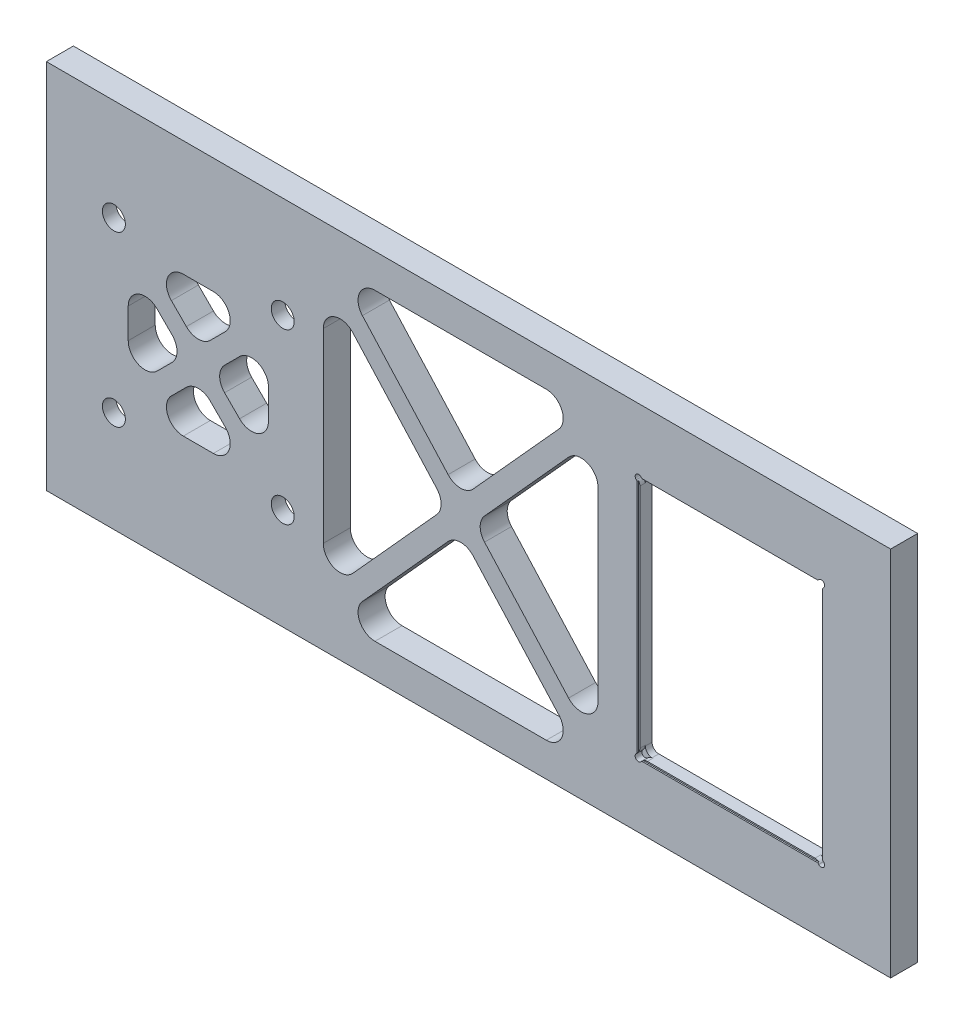
SolidWorks part; units mm, degrees
ref_plane "Front Plane" through (0, 0, 0) normal (0, 0, 1) x (1, 0, 0)
ref_plane "Top Plane" through (0, 0, 0) normal (0, 1, 0) x (1, 0, 0)
ref_plane "Right Plane" through (0, 0, 0) normal (1, 0, 0) x (0, 0, -1)
sketch "Sketch1" plane through (0, 0, 0) normal (0, 0, 1) x (1, 0, 0)
  line L0 (10, 27.5) -> (0, 27.5) construction
  line L1 (0, 0) -> (125, 0)
  line L2 (0, 0) -> (0, 55)
  line L3 (0, 55) -> (125, 55)
  line L4 (125, 0) -> (125, 55)
  line L5 (10, 40) -> (35, 40) construction
  line L6 (10, 40) -> (10, 15) construction
  line L7 (10, 15) -> (35, 15) construction
  line L8 (35, 40) -> (35, 15) construction
  line L9 (22.5, 27.5) -> (101.2, 27.5) construction
  line L10 (87.675, 45.425) -> (114.725, 45.425)
  line L11 (87.675, 45.425) -> (87.675, 9.575)
  line L12 (87.675, 9.575) -> (114.725, 9.575)
  line L13 (114.725, 45.425) -> (114.725, 9.575)
  line L14 (10, 40) -> (35, 15) construction
  line L15 (87.675, 45.425) -> (114.725, 9.575) construction
  circle A0 centre (10, 40) radius 1.7
  circle A1 centre (35, 40) radius 1.7
  circle A2 centre (10, 15) radius 1.7
  circle A3 centre (35, 15) radius 1.7
  dimension "D3" = 3.4
  dimension "D1" = 55
  dimension "D2" = 125
  dimension "D4" = 25
  dimension "D5" = 25
  dimension "D6" = 10
  dimension "D7" = 35.85
  dimension "D8" = 27.05
  dimension "D9" = 78.7
extrude "Boss-Extrude1" add sketch "Sketch1" along normal blind 4
sketch "Sketch2" plane through (0, 0, 4) normal (0, 0, 1) x (1, 0, 0)
  circle A0 centre (87.675, 45.425) radius 0.5
  circle A1 centre (114.725, 45.425) radius 0.5
  circle A2 centre (87.675, 9.575) radius 0.5
  circle A3 centre (114.725, 9.575) radius 0.5
  dimension "D1" = 1
extrude "Cut-Extrude1" cut sketch "Sketch2" against normal blind 1
fillet "Fillet1" radius 1 4 edges at (114.725, 9.575, 1.5) (87.675, 9.575, 1.5) (114.725, 45.425, 1.5) (87.675, 45.425, 1.5)
fillet "Fillet2" radius 1 8 edges at (114.2471, 9.7221, 3.5) (114.5779, 10.0529, 3.5) (87.8221, 10.0529, 3.5) (88.1529, 9.7221, 3.5) (114.5779, 44.9471, 3.5) (114.2471, 45.2779, 3.5) (87.8221, 44.9471, 3.5) (88.1529, 45.2779, 3.5)
sketch "Sketch3" plane through (125, 0, 0) normal (1, 0, 0) x (0, 0, -1)
  line L0 (-3.1, 42.5) -> (-3.1, 12.5) construction
  line L1 (-4, 0) -> (-4, 55) construction
  line L2 (-4, 27.5) -> (-3.1, 27.5) construction
  point P0 (-3.1, 42.5)
  point P1 (-3.1, 12.5)
  point P6 (-3.1, 27.5)
  dimension "D1" = 0.9
  dimension "D2" = 30
hole_wizard "M1.2x0.25 Tapped Hole1" [suppressed] positions "3DSketch2" profile "Sketch6" tap size "M1.2x0.25" standard "IS"
sketch3d "3DSketch2"
  point P0 (125, 42.5, 1.1)
  point P3 (125, 27.5, 1.1)
  point P6 (125, 12.5, 1.1)
sketch "Sketch6" plane through (125, 42.5, 1.1) normal (0, 1, 0) x (0, 0, -1)
  line L0 (0, 0) -> (0, 10.25)
  line L1 (0, 10.25) -> (0.475, 10.25)
  line L2 (0.475, 10.25) -> (0.475, 0)
  line L5 (0.475, 0) -> (0, 0)
  line L11 (0, -6.35) -> (0, 107.95) construction
  dimension "Thru Tap Drill Dia." = 0.95
  dimension "Thru Tap Drill Depth" = 10.25
cosmetic thread "Hole Thread1" [suppressed] parameters "D2"=1.2
cosmetic thread "Hole Thread2" [suppressed] parameters "D2"=1.2
cosmetic thread "Hole Thread3" [suppressed] parameters "D2"=1.2
sketch "Sketch7" plane through (0, 0, 4) normal (0, 0, 1) x (1, 0, 0)
  line L0 (87.475, 27.5) -> (114.925, 27.5) construction
  line L1 (87.475, 45.625) -> (114.925, 45.625)
  line L2 (87.475, 45.625) -> (87.475, 9.375)
  line L3 (87.475, 9.375) -> (114.925, 9.375)
  line L4 (114.925, 45.625) -> (114.925, 9.375)
  line L5 (114.725, 10.693) -> (114.725, 44.307) construction
  line L6 (113.607, 45.425) -> (88.793, 45.425) construction
  line L7 (87.475, 39.9467) -> (87.675, 39.9467) construction
  line L8 (87.675, 44.307) -> (87.675, 10.693) construction
  line L9 (90.6052, 45.425) -> (90.6052, 45.625) construction
  point P8 (114.725, 27.5)
  point P11 (101.2, 45.425)
  point P12 (101.2, 45.625)
  dimension "D1" = 0.2
extrude "Cut-Extrude2" cut sketch "Sketch7" against normal blind 0.2
sketch "Sketch8" plane through (0, 0, 0) normal (0, 0, -1) x (-1, 0, 0)
  line L0 (-116.225, 44.425) -> (-116.225, 10.575)
  line L1 (-113.725, 8.075) -> (-88.675, 8.075)
  line L2 (-86.175, 10.575) -> (-86.175, 44.425)
  line L3 (-88.675, 46.925) -> (-113.725, 46.925)
  line L4 (-114.725, 10.575) -> (-114.725, 44.425) construction
  arc A0 (-116.225, 10.575) -> (-113.725, 8.075) centre (-113.725, 10.575) ccw
  arc A1 (-88.675, 8.075) -> (-86.175, 10.575) centre (-88.675, 10.575) ccw
  arc A2 (-86.175, 44.425) -> (-88.675, 46.925) centre (-88.675, 44.425) ccw
  arc A3 (-113.725, 46.925) -> (-116.225, 44.425) centre (-113.725, 44.425) ccw
  arc A4 (-113.725, 45.425) -> (-114.725, 44.425) centre (-113.725, 44.425) ccw construction
  arc A5 (-87.675, 44.425) -> (-88.675, 45.425) centre (-88.675, 44.425) ccw construction
  arc A6 (-114.725, 10.575) -> (-113.725, 9.575) centre (-113.725, 10.575) ccw construction
  arc A7 (-88.675, 9.575) -> (-87.675, 10.575) centre (-88.675, 10.575) ccw construction
  dimension "D1" = 1.5
extrude "Cut-Extrude3" cut sketch "Sketch8" against normal blind 2
sketch "Sketch9" plane through (0, 0, 0) normal (0, 0, -1) x (-1, 0, 0)
  line L0 (-117.725, 44.425) -> (-117.725, 10.575)
  line L1 (-113.725, 6.575) -> (-88.675, 6.575)
  line L2 (-84.675, 10.575) -> (-84.675, 44.425)
  line L3 (-88.675, 48.425) -> (-113.725, 48.425)
  line L4 (-116.225, 44.425) -> (-116.225, 10.575) construction
  arc A0 (-117.725, 10.575) -> (-113.725, 6.575) centre (-113.725, 10.575) ccw
  arc A1 (-88.675, 6.575) -> (-84.675, 10.575) centre (-88.675, 10.575) ccw
  arc A2 (-84.675, 44.425) -> (-88.675, 48.425) centre (-88.675, 44.425) ccw
  arc A3 (-113.725, 48.425) -> (-117.725, 44.425) centre (-113.725, 44.425) ccw
  arc A4 (-113.725, 46.925) -> (-116.225, 44.425) centre (-113.725, 44.425) ccw construction
  arc A5 (-116.225, 10.575) -> (-113.725, 8.075) centre (-113.725, 10.575) ccw construction
  arc A6 (-88.675, 8.075) -> (-86.175, 10.575) centre (-88.675, 10.575) ccw construction
  arc A7 (-86.175, 44.425) -> (-88.675, 46.925) centre (-88.675, 44.425) ccw construction
  dimension "D1" = 1.5
extrude "Cut-Extrude4" cut sketch "Sketch9" against normal blind 1
sketch "Sketch10" plane through (0, 0, 0) normal (0, 0, -1) x (-1, 0, 0)
  line L0 (0, 55) -> (0, 0) construction
  line L5 (-32.8787, 37.8787) -> (-12.1213, 37.8787) construction
  line L6 (-32.8787, 37.8787) -> (-32.8787, 17.1213) construction
  line L7 (-32.8787, 17.1213) -> (-12.1213, 17.1213) construction
  line L8 (-12.1213, 37.8787) -> (-12.1213, 17.1213) construction
  line L9 (-24.6213, 27.5) -> (-22.5, 29.6213) construction
  line L10 (-35, 40) -> (-10, 15) construction
  line L11 (-35, 40) -> (-10, 40) construction
  line L12 (-35, 40) -> (-35, 15) construction
  line L13 (-35, 15) -> (-10, 15) construction
  line L14 (-10, 40) -> (-10, 15) construction
  line L15 (-12.1213, 37.8787) -> (-32.8787, 17.1213) construction
  line L16 (-32.8787, 35.7574) -> (-24.6213, 27.5)
  line L17 (-24.6213, 27.5) -> (-32.8787, 19.2426)
  line L18 (-32.8787, 19.2426) -> (-32.8787, 35.7574)
  line L19 (-30.7574, 37.8787) -> (-14.2426, 37.8787)
  line L20 (-14.2426, 37.8787) -> (-22.5, 29.6213)
  line L21 (-22.5, 29.6213) -> (-30.7574, 37.8787)
  line L22 (-30.7574, 17.1213) -> (-22.5, 25.3787)
  line L23 (-22.5, 25.3787) -> (-14.2426, 17.1213)
  line L24 (-14.2426, 17.1213) -> (-30.7574, 17.1213)
  line L25 (-12.1213, 35.7574) -> (-20.3787, 27.5)
  line L26 (-20.3787, 27.5) -> (-12.1213, 19.2426)
  line L27 (-12.1213, 19.2426) -> (-12.1213, 35.7574)
  line L28 (-20.3787, 27.5) -> (-22.5, 29.6213) construction
  point P9 (-12.1213, 27.5)
  point P12 (0, 27.5)
  dimension "D1" = 3
  dimension "D2" = 3
extrude "Cut-Extrude5" cut sketch "Sketch10" against normal through all
sketch "Sketch11" plane through (0, 0, 0) normal (0, 0, -1) x (-1, 0, 0)
  line L5 (-81.675, 50) -> (-41, 50) construction
  line L6 (-81.675, 50) -> (-81.675, 5) construction
  line L7 (-81.675, 5) -> (-41, 5) construction
  line L8 (-41, 50) -> (-41, 5) construction
  line L9 (-63.3595, 27.5) -> (-61.3375, 29.7369) construction
  line L10 (-81.675, 50) -> (-41, 5) construction
  line L15 (-41, 50) -> (-81.675, 5) construction
  line L16 (-81.675, 47.7631) -> (-63.3595, 27.5)
  line L17 (-63.3595, 27.5) -> (-81.675, 7.2369)
  line L18 (-81.675, 7.2369) -> (-81.675, 47.7631)
  line L19 (-79.653, 50) -> (-43.022, 50)
  line L20 (-43.022, 50) -> (-61.3375, 29.7369)
  line L21 (-61.3375, 29.7369) -> (-79.653, 50)
  line L22 (-79.653, 5) -> (-61.3375, 25.2631)
  line L23 (-61.3375, 25.2631) -> (-43.022, 5)
  line L24 (-43.022, 5) -> (-79.653, 5)
  line L25 (-41, 47.7631) -> (-59.3155, 27.5)
  line L26 (-59.3155, 27.5) -> (-41, 7.2369)
  line L27 (-41, 7.2369) -> (-41, 47.7631)
  line L28 (-59.3155, 27.5) -> (-61.3375, 29.7369) construction
  line L29 (-32.8787, 35.7574) -> (-32.8787, 19.2426) construction
  line L30 (-84.675, 10.575) -> (-84.675, 44.425) construction
  circle A0 centre (-35, 15) radius 1.7 construction
  point P3 (-32.8787, 27.5)
  point P9 (-41, 27.5)
  dimension "D1" = 3
  dimension "D2" = 3
  dimension "D3" = 6
  dimension "D4" = 45
extrude "Cut-Extrude6" cut sketch "Sketch11" against normal through all
fillet "Fillet3" radius 2.5 24 edges at (12.1213, 19.2426, 2) (20.3787, 27.5, 2) (12.1213, 35.7574, 2) (14.2426, 17.1213, 2) (30.7574, 17.1213, 2) (22.5, 25.3787, 2) (32.8787, 19.2426, 2) (24.6213, 27.5, 2) (14.2426, 37.8787, 2) (30.7574, 37.8787, 2) (32.8787, 35.7574, 2) (22.5, 29.6213, 2) (79.653, 5, 2) (43.022, 5, 2) (41, 7.2369, 2) (41, 47.7631, 2) (59.3155, 27.5, 2) (43.022, 50, 2) (81.675, 7.2369, 2) (61.3375, 25.2631, 2) (63.3595, 27.5, 2) (81.675, 47.7631, 2) (79.653, 50, 2) (61.3375, 29.7369, 2)
sketch "Sketch12" plane through (0, 0, 0) normal (0, 0, -1) x (-1, 0, 0)
  circle A0 centre (-35, 40) radius 5
  circle A1 centre (-10, 40) radius 5
  circle A2 centre (-35, 15) radius 5
  circle A3 centre (-10, 15) radius 5
  dimension "D1" = 10
extrude "Cut-Extrude7" cut sketch "Sketch12" against normal blind 2
